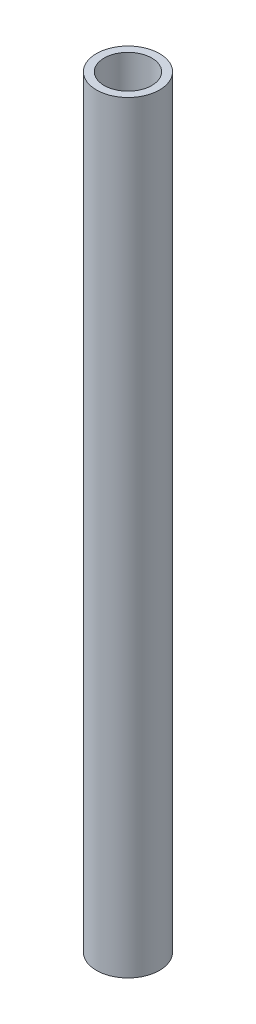
SolidWorks part; units mm, degrees
material "Thornel Mat VMA"
ref_plane "Front Plane" through (0, 0, 0) normal (0, 0, 1) x (1, 0, 0)
ref_plane "Top Plane" through (0, 0, 0) normal (0, 1, 0) x (1, 0, 0)
ref_plane "Right Plane" through (0, 0, 0) normal (1, 0, 0) x (0, 0, -1)
sketch "Sketch1" plane through (0, 0, 0) normal (0, 1, 0) x (1, 0, 0)
  circle A1 centre (0, 0) radius 3.175
  circle A2 centre (0, 0) radius 4.2037
  dimension "D1" = 6.35
  dimension "D2" = 8.4074
extrude "Boss-Extrude1" add sketch "Sketch1" along normal blind 101.6
